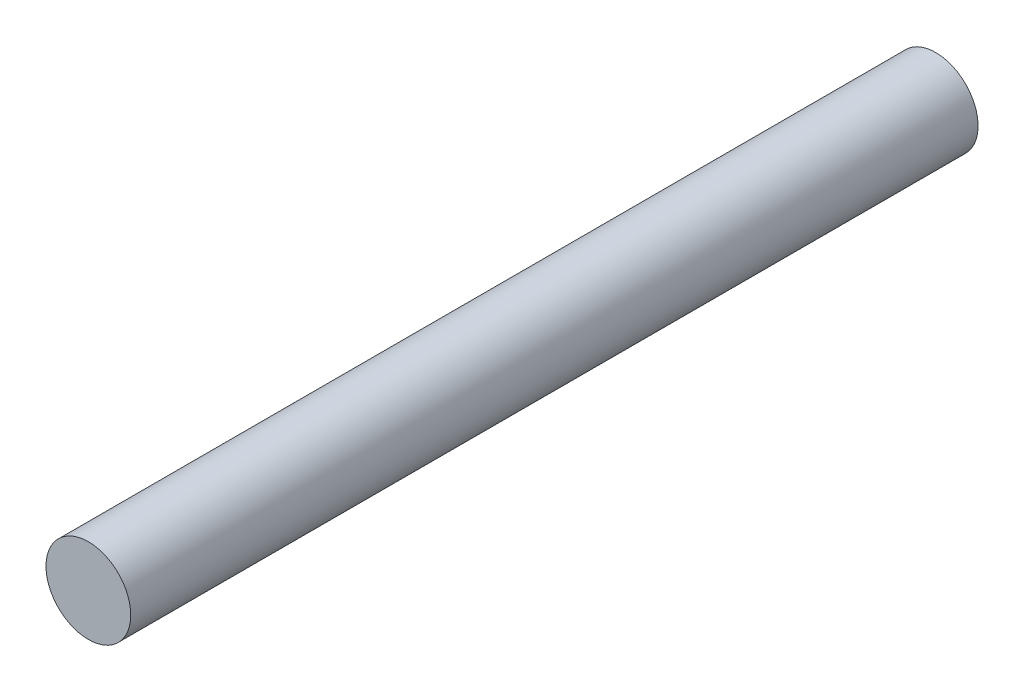
SolidWorks part; units mm, degrees
ref_plane "Front Plane" through (0, 0, 0) normal (0, 0, 1) x (1, 0, 0)
ref_plane "Top Plane" through (0, 0, 0) normal (0, 1, 0) x (1, 0, 0)
ref_plane "Right Plane" through (0, 0, 0) normal (1, 0, 0) x (0, 0, -1)
sketch "Sketch1" plane through (0, 0, 0) normal (0, 0, 1) x (1, 0, 0)
  line L1 (-6.35, 0) -> (6.35, 0) construction
  dimension "OD" = 12.7
sketch "Sketch2" plane through (0, 0, 0) normal (1, 0, 0) x (0, 0, -1)
  line L0 (76.2, 0) -> (-76.2, 0)
  point P0 (-63.5, 0)
  point P3 (63.5, 0)
  point P4 (0, 0)
  dimension "Length" = 152.4
  dimension "D1" = 12.7
  dimension "D2" = 12.7
sketch "Sketch3" plane through (0, 0, 0) normal (0, 0, 1) x (1, 0, 0)
  circle A0 centre (0, 0) radius 6.35
extrude "Boss-Extrude1" add sketch "Sketch3" along normal up to vertex (76.2 mm away) and the other way up to vertex (76.2 mm away) up to point (0, 0, 76.2) other way up to point (0, 0, -76.2)
sketch "Sketch4" plane through (0, 0, -76.2) normal (0, 0, -1) x (-1, 0, 0)
  circle A0 centre (0, 0) radius 6.35 construction
  circle A1 centre (0, 0) radius 6.35
extrude "Cut-Extrude1" cut sketch "Sketch4" against normal blind 25.4
hole_wizard "1/4 (0.25) Diameter Hole1" positions "3DSketch1" profile "Sketch6" hole size "1/4" standard "ANSI Inch"
sketch3d "3DSketch1"
  line L0 (0, 0, 76.2) -> (0, 0, -50.8) construction
  circle A0 centre (0, 0, -50.8) radius 6.35 construction
  point P0 (0, 0, -50.8)
  point P8 (0, 0, -57.15)
sketch "Sketch6" plane through (0, 0, -50.8) normal (1, 0, 0) x (0, 1, 0)
  line L0 (0, 0) -> (0, 40.0077)
  line L1 (0, 40.0077) -> (3.175, 38.1)
  line L2 (3.175, 38.1) -> (3.175, 0)
  line L5 (3.175, 0) -> (0, 0)
  line L10 (0, 40.0077) -> (-3.175, 38.1) construction
  line L11 (0, -6.35) -> (0, 107.95) construction
  dimension "Hole Dia." = 6.35
  dimension "Hole Depth" = 38.1
  dimension "Drill Angle" = 118
thread "Thread1" pitch 1.27 method cut profile "Thread Profile1" start angle 0, offset 0, length 31.75, pitch 1.27, diameter 6.35
ref_plane "Plane1" through (3.175, 0, -50.8) normal (0, -1, 0) x (1, 0, 0)
sketch "Thread Profile1" plane through (3.175, 0, -50.8) normal (0, -1, 0) x (1, 0, 0)
  line L0 (0, 0) -> (0, 1.27) construction
  line L1 (0, 0) -> (0.6874, 0.3969)
  line L2 (0.6874, 0.3969) -> (0.6874, 0.5556)
  line L3 (0.6874, 0.5556) -> (0, 0.9525)
  line L4 (0.6874, 0.4762) -> (0, 0.4762) construction
  line L11 (0, 0) -> (0, 0.9525)
  point P2 (0, 0)
  dimension "Pitch" = 1.27
  dimension "Profile_Angle" = 60
  dimension "Profile_Land" = 0.1588
  dimension "Profile_Height" = 0.6874
equation "\"D1@Sketch2\"=\"Length@Sketch2\"/12"
equation "\"D2@Sketch2\"=\"Length@Sketch2\"/12"
